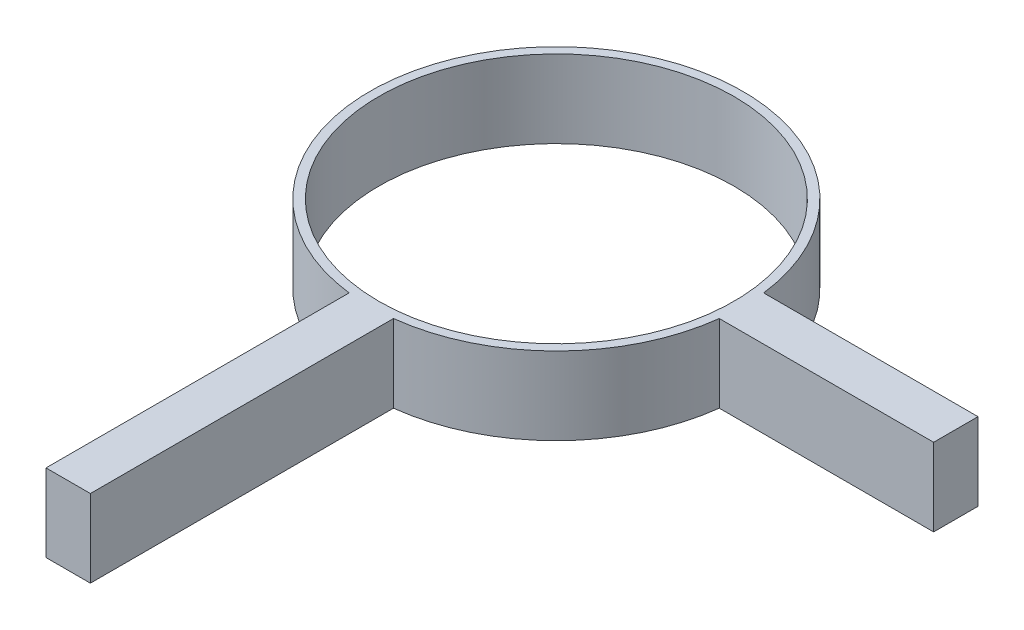
SolidWorks part; units mm, degrees
ref_plane "Front Plane" through (0, 0, 0) normal (0, 0, 1) x (1, 0, 0)
ref_plane "Top Plane" through (0, 0, 0) normal (0, 1, 0) x (1, 0, 0)
ref_plane "Right Plane" through (0, 0, 0) normal (1, 0, 0) x (0, 0, -1)
sketch "Sketch1" plane through (0, 0, 0) normal (0, 1, 0) x (1, 0, 0)
  line L1 (-2, -16.6805) -> (-2, -44)
  line L2 (-2, -44) -> (2, -44)
  line L3 (2, -44) -> (2, -16.6805)
  line L6 (16.6805, 2) -> (36, 2)
  line L7 (36, 2) -> (36, -2)
  line L8 (36, -2) -> (16.6805, -2)
  circle A0 centre (0, 0) radius 16
  circle A1 centre (0, 0) radius 16.8
  point P3 (0, 0)
  point P12 (0, -44)
  point P13 (36, 0)
  point P15 (16.6, 0)
  dimension "D1" = 32
  dimension "D5" = 4
  dimension "D6" = 36
  dimension "D3" = 44
  dimension "D4" = 4
  dimension "D2" = 0.8
extrude "Boss-Extrude1" add sketch "Sketch1" along normal blind 7 contours A0 | A1 L1 L2 L3 | A1 L8 L7 L6 region at (0, 0, 30.3801) region at (-11.5434, 0, -11.5434) region at (26.3801, 0, 0)
